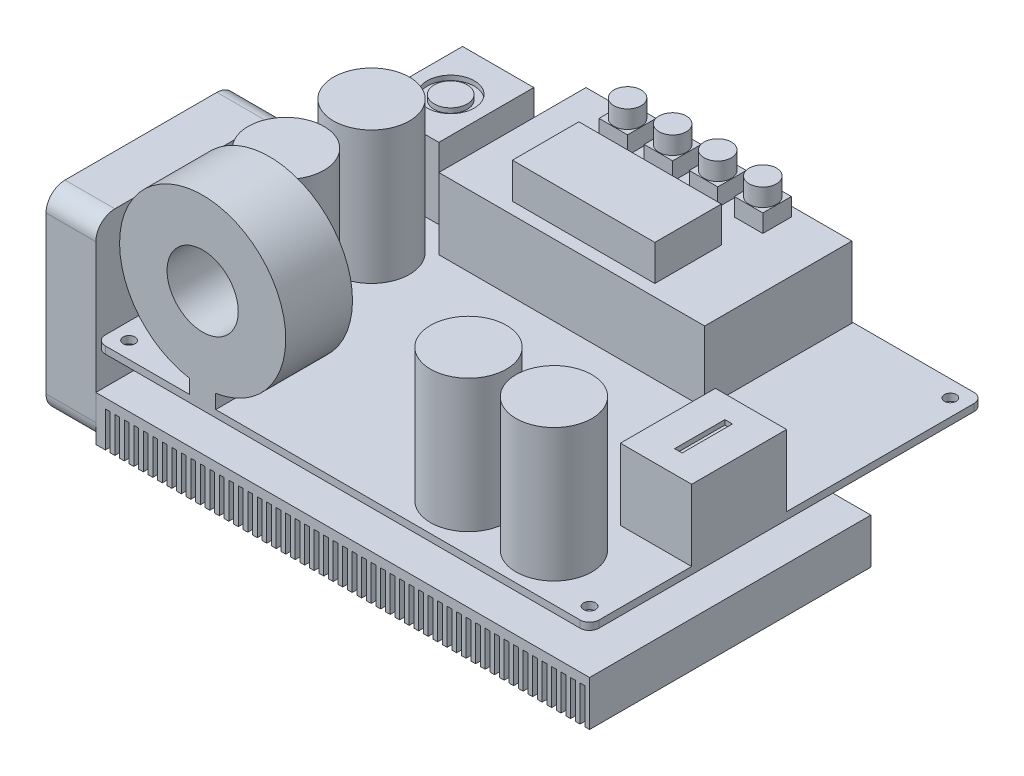
SolidWorks part; units mm, degrees
ref_plane "Front Plane" through (0, 0, 0) normal (0, 0, 1) x (1, 0, 0)
ref_plane "Top Plane" through (0, 0, 0) normal (0, 1, 0) x (1, 0, 0)
ref_plane "Right Plane" through (0, 0, 0) normal (1, 0, 0) x (0, 0, -1)
sketch "Sketch1" plane through (0, 0, 0) normal (0, 1, 0) x (1, 0, 0)
  line L0 (-52, -41.5) -> (-52, 41.5)
  line L1 (-52, -41.5) -> (52, -41.5)
  line L2 (-52, 41.5) -> (52, 41.5)
  line L3 (52, -41.5) -> (52, 41.5)
  line L4 (-52, -41.5) -> (52, 41.5) construction
  line L5 (-52, 41.5) -> (52, -41.5) construction
  point P1 (0, 0)
  dimension "D1" = 104
  dimension "D2" = 83
extrude "Boss-Extrude1" add sketch "Sketch1" along normal blind 0.75 and the other way blind 0.75
sketch "Sketch2" plane through (0, 0.75, 0) normal (0, 1, 0) x (1, 0, 0)
  line L0 (52, -41.5) -> (52, -38)
  line L1 (52, -41.5) -> (52, 41.5) construction
  line L2 (52, -38) -> (48.5, -38)
  circle A0 centre (48.5, -38) radius 1.25
  dimension "D3" = 2.5
  dimension "D1" = 3.5
  dimension "D2" = 3.5
extrude "Cut-Extrude1" cut sketch "Sketch2" against normal through all contours A0
mirror "Mirror1" about plane through (0, 0, 0) normal (1, 0, 0) of "Cut-Extrude1"
mirror "Mirror2" about plane through (0, 0, 0) normal (0, 0, 1) of "Mirror1"
fillet "Fillet1" radius 2 1 edges at (52, 0, 41.5) type face fillet first side face at (0, 0, 41.5) second side face at (52, 0, 0)
fillet "Fillet2" radius 2 1 edges at (-52, 0, 41.5) type face fillet first side face at (-1, 0, 41.5) second side face at (-52, 0, 0)
fillet "Fillet3" radius 2 1 edges at (-52, 0, -41.5) type face fillet first side face at (-52, 0, -1) second side face at (0, 0, -41.5)
fillet "Fillet4" radius 2 1 edges at (52, 0, -41.5) type face fillet first side face at (1, 0, -41.5) second side face at (52, 0, -1)
ref_plane "Plane1" through (0, -8.75, 0) normal (0, -1, 0) x (-1, 0, 0)
sketch "Sketch5" plane through (0, -8.75, 0) normal (0, -1, 0) x (-1, 0, 0)
  line L0 (0, 0) -> (0, -41.5)
  line L1 (0, -41.5) -> (-52, -41.5)
  line L2 (0, 0) -> (0, 17.75)
  line L4 (0, 17.75) -> (-52, 17.75)
  line L5 (0, 17.75) -> (0, -41.5)
  line L6 (0, -41.5) -> (-52, -41.5)
  line L7 (-52, 17.75) -> (-52, -41.5)
  dimension "D1" = 41.5
  dimension "D2" = 52
  dimension "D3" = 17.75
extrude "Boss-Extrude2" add sketch "Sketch5" along normal blind 9.5 separate body contours L4 L7 L1 L0 L2 region at (26, -8.75, 11.875)
mirror "Mirror7" about plane through (0, 0, 0) normal (1, 0, 0) of "Boss-Extrude2"
sketch "Sketch7" plane through (0, -18.25, 0) normal (0, -1, 0) x (-1, 0, 0)
  line L0 (-52, -41.5) -> (-51, -41.5)
  line L1 (52, -41.5) -> (-52, -41.5) construction
  line L2 (-51, -41.5) -> (-50, -41.5)
  line L3 (-50, -41.5) -> (-50, 17.75)
  line L4 (52, 17.75) -> (-52, 17.75) construction
  line L5 (-50, 17.75) -> (-51, 17.75)
  line L6 (-51, 17.75) -> (-51, -41.5)
extrude "Cut-Extrude2" cut sketch "Sketch7" against normal blind 7.5
pattern_linear "LPattern1" count 51 spacing 2 along (-1, 0, 0) of "Cut-Extrude2"
sketch "Sketch8" plane through (0, 0.75, 0) normal (0, 1, 0) x (1, 0, 0)
  line L0 (52, 0) -> (52, -20)
  line L1 (52, -39.5) -> (52, 39.5) construction
  line L2 (52, -20) -> (37, -20)
  line L3 (37, -20) -> (37, 0)
  line L4 (37, 0) -> (52, 0)
  line L5 (-48.5, 36.75) -> (-48.5, 35.75)
  line L6 (-48.5, 35.75) -> (-52, 35.75)
  line L7 (-52, 39.5) -> (-52, -39.5) construction
  line L8 (-52, 35.75) -> (-52, 15.75)
  line L9 (-52, 15.75) -> (-37, 15.75)
  line L10 (-37, 15.75) -> (-37, 35.75)
  line L11 (-37, 35.75) -> (-48.5, 35.75)
  circle A0 centre (-48.5, 38) radius 1.25 construction
  line M5 (52, -39.5) -> (52, 39.5)
  line M9 (-52, 39.5) -> (-52, -39.5)
extrude "Boss-Extrude3" add sketch "Sketch8" along normal blind 15 contours L4 L3 L2 M5 | L10 L11 L6 L9 M9 region at (44.5, 0.75, 10) region at (-44.5, 0.75, -25.75)
sketch "Sketch9" plane through (0, 15.75, 0) normal (0, 1, 0) x (1, 0, 0)
  line L0 (37, -10) -> (52, -10)
  line L1 (37, -20) -> (37, 0) construction
  line L2 (52, -20) -> (52, 0) construction
  line L3 (45.291, -4.6962) -> (43.709, -4.6962)
  line L4 (45.291, -4.6962) -> (45.291, -15.3038)
  line L5 (43.709, -4.6962) -> (43.709, -15.3038)
  line L6 (45.291, -15.3038) -> (43.709, -15.3038)
  line L7 (45.291, -4.6962) -> (43.709, -15.3038) construction
  line L8 (43.709, -4.6962) -> (45.291, -15.3038) construction
  point P7 (44.5, -10)
extrude "Cut-Extrude3" cut sketch "Sketch9" against normal blind 1 contours L6 L4 L0 L5 | L3 L5 L0 L4 region at (44.5, 15.75, 7.3481) region at (44.5, 15.75, 12.6519)
sketch "Sketch10" plane through (0, 15.75, 0) normal (0, 1, 0) x (1, 0, 0)
  line L0 (-37, 25.75) -> (-52, 25.75)
  line L1 (-37, 15.75) -> (-37, 35.75) construction
  line L2 (-52, 35.75) -> (-52, 15.75) construction
  circle A0 centre (-44.5, 25.75) radius 3.4784
  circle A1 centre (-44.5, 25.75) radius 4.9745
extrude "Cut-Extrude4" cut sketch "Sketch10" against normal blind 1 contours L0 A1 A0 | L0 A1 A0 region at (-44.5, 15.75, -20.8868) region at (-40.2736, 15.75, -25.8612)
sketch "Sketch12" plane through (0, 0.75, 0) normal (0, 1, 0) x (1, 0, 0)
  line L0 (-50, -41.5) -> (-29.5, -41.5)
  line L1 (-50, -41.5) -> (50, -41.5) construction
  line L2 (-29.5, -41.5) -> (-29.5, -34.4689)
  line L3 (-29.5, -41.5) -> (-12, -41.5)
  line L4 (-47, -27.4377) -> (-47, -41.5)
  line L5 (-47, -27.4377) -> (-12, -27.4377)
  line L6 (-47, -41.5) -> (-12, -41.5)
  line L7 (-12, -27.4377) -> (-12, -41.5)
  line L8 (-47, -27.4377) -> (-12, -41.5) construction
  line L9 (-47, -41.5) -> (-12, -27.4377) construction
  line M13 (-50, -41.5) -> (50, -41.5)
  dimension "D1" = 20.5
  dimension "D2" = 17.5
extrude "Boss-Extrude4" add sketch "Sketch12" along normal blind 38 contours L7 L5 L4 L0 M13 region at (-46.6228, 0.75, 34.4689)
sketch "Sketch13" plane through (0, 0.75, 0) normal (0, 1, 0) x (1, 0, 0)
  line L0 (-52, -39.5) -> (-52, -1.5)
  line L1 (-52, 15.75) -> (-52, -39.5) construction
  line L2 (-52, -1.5) -> (-62.5, -1.5)
  line L3 (-62.5, -1.5) -> (-62.5, -41.5)
  line L4 (-62.5, -41.5) -> (-52, -41.5)
  line L5 (-52, -41.5) -> (-52, -39.5)
  dimension "D1" = 38
  dimension "D2" = 10.5
extrude "Boss-Extrude5" add sketch "Sketch13" along normal blind 22 and the other way up to surface (19 mm away) separate body other way up to face at (-51, -18.25, 11.875)
fillet "Fillet5" radius 4 1 edges at (-57.25, 22.75, 41.5) type face fillet first side face at (-57.25, 2.25, 41.5) second side face at (-57.25, 22.75, 21.5)
fillet "Fillet6" radius 4 1 edges at (-57.25, 22.75, 1.5) type face fillet first side face at (-57.25, 22.75, 19.5) second side face at (-57.25, 2.25, 1.5)
fillet "Fillet7" radius 4 1 edges at (-57.25, -18.25, 41.5) type face fillet first side face at (-57.25, 0.25, 41.5) second side face at (-57.25, -18.25, 21.5)
fillet "Fillet8" radius 4 1 edges at (-57.25, -18.25, 1.5) type face fillet first side face at (-57.25, -18.25, 19.5) second side face at (-57.25, 0.25, 1.5)
sketch "Sketch14" plane through (0, 0.75, 0) normal (0, 1, 0) x (1, 0, 0)
  line L0 (-47, -27.4377) -> (-47, -14.4377)
  line L1 (-47, -14.4377) -> (-39, -14.4377)
  line L2 (-39, -14.4377) -> (-39, 3.5623)
  line L3 (50, -39.5) -> (34.5, -39.5)
  line L4 (34.5, -39.5) -> (34.5, -31.5)
  line L5 (34.5, -31.5) -> (16.5, -31.5)
  circle A0 centre (-39, 3.5623) radius 8
  circle A1 centre (-39, -14.4377) radius 8
  circle A2 centre (34.5, -31.5) radius 8
  circle A3 centre (16.5, -31.5) radius 8
  dimension "D4" = 16
  dimension "D5" = 16
  dimension "D8" = 16
  dimension "D10" = 16
  dimension "D1" = 13
  dimension "D2" = 8
  dimension "D3" = 18
  dimension "D6" = 15.5
  dimension "D7" = 8
  dimension "D9" = 18
extrude "Boss-Extrude6" add sketch "Sketch14" along normal blind 28 contours A0 | L1 A1 L2 | A3 | L4 A2 L5 | L5 A2 L4 | L2 A1 L1 region at (-42.3953, 0.75, 11.0424) region at (-37.8682, 0.75, 15.5695) region at (-44.4969, 0.75, -9.0591) region at (31.1047, 0.75, 34.8953) region at (35.6318, 0.75, 30.3682) region at (8.7263, 0.75, 31.5)
sketch "Sketch16" plane through (0, 0, 41.5) normal (0, 0, 1) x (1, 0, 0)
  line L0 (-26.75, 0.75) -> (-26.75, 3.7174)
  line L1 (-29.5, 0.75) -> (-29.5, 3.5)
  line L2 (-29.5, 3.5) -> (-29.5, 21)
  line L3 (-29.5, 0.75) -> (-32.25, 0.75)
  line L5 (-47, 0.75) -> (-47, 38.75)
  line L6 (-47, 38.75) -> (-12, 38.75)
  line L7 (-12, 0.75) -> (-12, 38.75)
  line L8 (-32.25, 0.75) -> (-32.25, 3.7174)
  line L9 (-29.5, 0.75) -> (-26.75, 0.75)
  line L10 (-47, 0.75) -> (-32.25, 0.75)
  line L11 (-26.75, 0.75) -> (-12, 0.75)
  circle A0 centre (-29.5, 21) radius 17.5
  circle A1 centre (-29.5, 21) radius 7.5
  line M8 (-12, 0.75) -> (-12, 38.75)
  line M9 (-12, 38.75) -> (-47, 38.75)
  line M10 (-47, 38.75) -> (-47, 0.75)
  dimension "D3" = 35
  dimension "D4" = 15
  dimension "D1" = 2.75
  dimension "D2" = 17.5
extrude "Cut-Extrude6" cut sketch "Sketch16" against normal up to next (14.0623 mm away) contours A0 L5 L10 L8 | A0 L0 L11 M8 | A1 | A0 L7 M9 M10 region at (-17.2126, 5.3958, 41.5) region at (-34.6533, 26.1533, 41.5) region at (-29.5, 38.5392, 41.5) region at (-41.7874, 5.3958, 41.5)
sketch "Sketch18" plane through (0, 15.75, 0) normal (0, 1, 0) x (1, 0, 0)
  line L0 (-52, 25.75) -> (-31.5, 25.75)
  line L1 (-52, 35.75) -> (-52, 15.75) construction
  line L2 (-31.5, 25.75) -> (-31.5, 10.25)
  line L3 (-31.5, 25.75) -> (-3.5, 25.75)
  line L4 (24.5, 41.25) -> (24.5, 10.25)
  line L5 (24.5, 41.25) -> (-31.5, 41.25)
  line L6 (24.5, 10.25) -> (-31.5, 10.25)
  line L7 (-31.5, 41.25) -> (-31.5, 10.25)
  line L8 (24.5, 41.25) -> (-31.5, 10.25) construction
  line L9 (24.5, 10.25) -> (-31.5, 41.25) construction
  dimension "D1" = 20.5
  dimension "D2" = 15.5
  dimension "D3" = 28
extrude "Boss-Extrude7" add sketch "Sketch18" against normal up to next contours L5 L7 L2 L6 L4 region at (-30.8599, 15.75, -33.5)
sketch "Sketch19" plane through (0, 15.75, 0) normal (0, 1, 0) x (1, 0, 0)
  line L0 (-3.5, 41.25) -> (-3.5, 36.25)
  line L1 (24.5, 41.25) -> (-31.5, 41.25) construction
  line L2 (-3.5, 36.25) -> (-8.25, 36.25)
  line L3 (-5.25, 33.25) -> (-11.25, 33.25)
  line L4 (-5.25, 33.25) -> (-5.25, 39.25)
  line L5 (-11.25, 33.25) -> (-11.25, 39.25)
  line L6 (-5.25, 39.25) -> (-11.25, 39.25)
  line L7 (-5.25, 33.25) -> (-11.25, 39.25) construction
  line L8 (-11.25, 33.25) -> (-5.25, 39.25) construction
  dimension "D1" = 5
  dimension "D2" = 4.75
  dimension "D3" = 6
  dimension "D4" = 6
extrude "Boss-Extrude8" add sketch "Sketch19" along normal blind 3.75 contours L4 L6 L5 L3 region at (-8.25, 15.75, -33.3349)
sketch "Sketch20" plane through (0, 19.5, 0) normal (0, 1, 0) x (1, 0, 0)
  line L0 (-8.25, 33.25) -> (-8.25, 39.25)
  line L1 (-5.25, 33.25) -> (-11.25, 33.25) construction
  line L2 (-5.25, 39.25) -> (-11.25, 39.25) construction
  circle A0 centre (-8.25, 36.25) radius 2.875
  dimension "D1" = 5.75
extrude "Boss-Extrude9" add sketch "Sketch20" along normal blind 3.75 contours A0
pattern_linear "LPattern2" count 2 spacing 9.5 along (-1, 0, 0) count 3 spacing 9.5 along (1, 0, 0) of "Boss-Extrude8", "Boss-Extrude9"
sketch "Sketch21" plane through (0, 15.75, 0) normal (0, 1, 0) x (1, 0, 0)
  line L0 (-3.5, 10.25) -> (-3.5, 19.75)
  line L1 (24.5, 10.25) -> (-31.5, 10.25) construction
  line L2 (-3.5, 19.75) -> (-3.5, 26.75)
  line L3 (-3.5, 26.75) -> (11.5, 26.75)
  line L4 (-18.5, 12.75) -> (-18.5, 26.75)
  line L5 (-18.5, 12.75) -> (11.5, 12.75)
  line L6 (-18.5, 26.75) -> (11.5, 26.75)
  line L7 (11.5, 12.75) -> (11.5, 26.75)
  line L8 (-18.5, 12.75) -> (11.5, 26.75) construction
  line L9 (-18.5, 26.75) -> (11.5, 12.75) construction
  dimension "D1" = 9.5
  dimension "D2" = 7
  dimension "D3" = 15
extrude "Boss-Extrude10" add sketch "Sketch21" along normal blind 7.5 contours L6 L4 L5 L0 L2 | L5 L7 L3 L2 L0 region at (-11, 15.75, -19.75) region at (4, 15.75, -19.75)
